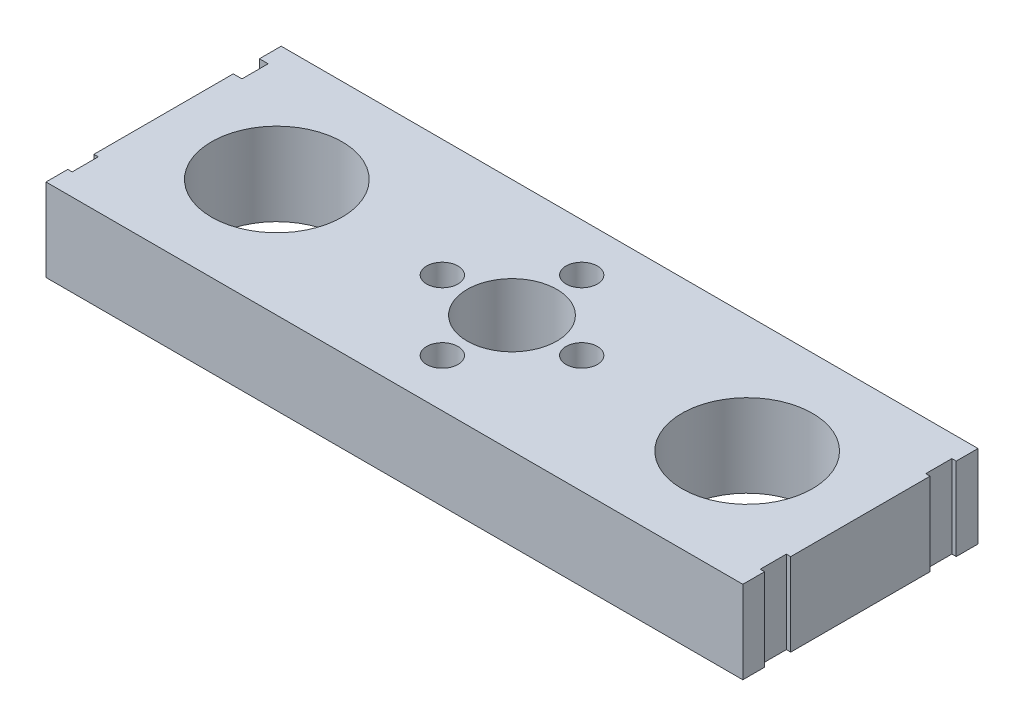
SolidWorks part; units mm, degrees
ref_plane "前视基准面" through (0, 0, 0) normal (0, 0, 1) x (1, 0, 0)
ref_plane "上视基准面" through (0, 0, 0) normal (0, 1, 0) x (1, 0, 0)
ref_plane "右视基准面" through (0, 0, 0) normal (1, 0, 0) x (0, 0, -1)
sketch "草图1" plane through (0, 0, 0) normal (0, 1, 0) x (1, 0, 0)
  line L1 (-40, 13.5) -> (40, 13.5)
  line L2 (-40, 13.5) -> (-40, -13.5)
  line L3 (-40, -13.5) -> (40, -13.5)
  line L4 (40, 13.5) -> (40, -13.5)
  line L5 (-40, 13.5) -> (40, -13.5) construction
  line L6 (-40, -13.5) -> (40, 13.5) construction
  point P0 (0, 0)
  dimension "D1" = 80
  dimension "D2" = 27
extrude "凸台-拉伸1" add sketch "草图1" along normal blind 9.5
sketch "草图2" plane through (0, 0, 0) normal (0, -1, 0) x (1, 0, 0)
  line L0 (-40, 0) -> (40, 0) construction
  line L1 (-40, -13.5) -> (-40, 13.5) construction
  line L2 (40, 13.5) -> (40, -13.5) construction
ref_plane "基准面1" through (0, 0, 0) normal (0, 0, 1) x (1, 0, 0)
sketch "草图3" plane through (0, 9.5, 0) normal (0, 1, 0) x (1, 0, 0)
  line L0 (-14.85, 0) -> (14.85, 0) construction
  line L1 (0, 13.5) -> (0, -13.5) construction
  line L2 (40, 13.5) -> (-40, 13.5) construction
  line L3 (-40, -13.5) -> (40, -13.5) construction
  circle A0 centre (-27, 0) radius 7.5
  circle A1 centre (27, 0) radius 7.5
  dimension "D1" = 15
  dimension "D2" = 54
extrude "切除-拉伸1" cut sketch "草图3" against normal through all contours A1 | A0
sketch "草图4" plane through (0, 9.5, 0) normal (0, 1, 0) x (1, 0, 0)
  line L0 (-40, 0) -> (40, 0) construction
  circle A0 centre (0, 0) radius 5.15
  dimension "D1" = 10.3
extrude "切除-拉伸2" cut sketch "草图4" against normal through all
sketch "草图5" plane through (0, 9.5, 0) normal (0, 1, 0) x (1, 0, 0)
  circle A4 centre (8, 0) radius 1.8
  circle A8 centre (-8, 0) radius 1.8
  circle A9 centre (0, 8) radius 1.8
  circle A10 centre (0, -8) radius 1.8
  dimension "D1" = 3.6
extrude "切除-拉伸3" cut sketch "草图5" against normal through all
ref_plane "基准面2" through (0, 4.5, 0) normal (0, 1, 0) x (1, 0, 0)
sketch "草图6" plane through (0, 4.5, 0) normal (0, 1, 0) x (1, 0, 0)
  line L0 (-40, 9.5) -> (40, 9.5) construction
  line L1 (-40, 13.5) -> (-40, -13.5) construction
  line L2 (40, -13.5) -> (40, 13.5) construction
  line L3 (-40, -9.5) -> (40, -9.5) construction
  line L4 (-40, -13.5) -> (40, -13.5) construction
  line L5 (40, 13.5) -> (-40, 13.5) construction
  dimension "D1" = 4
  dimension "D2" = 4
sketch "草图7" plane through (0, 9.5, 0) normal (0, 1, 0) x (1, 0, 0)
  line L0 (40, -13.5) -> (40, 13.5) construction
  line L1 (40, 11.0016) -> (39.5, 11.0016)
  line L2 (40, 11.0016) -> (40, 8.0016)
  line L3 (40, 8.0016) -> (39.5, 8.0016)
  line L4 (39.5, 11.0016) -> (39.5, 8.0016)
  line L13 (40, -7.9999) -> (39.5, -7.9999)
  line L14 (40, -7.9999) -> (40, -10.9999)
  line L15 (40, -10.9999) -> (39.5, -10.9999)
  line L16 (39.5, -7.9999) -> (39.5, -10.9999)
  line L17 (-40, 13.5) -> (-40, -13.5) construction
  line L18 (-40, 11.0016) -> (-39, 11.0016)
  line L19 (-40, 11.0016) -> (-40, 8.0016)
  line L20 (-40, 8.0016) -> (-39, 8.0016)
  line L21 (-39, 11.0016) -> (-39, 8.0016)
  line L23 (-40, -7.9999) -> (-39.5, -7.9999)
  line L24 (-40, -7.9999) -> (-40, -10.9999)
  line L25 (-40, -10.9999) -> (-39.5, -10.9999)
  line L26 (-39.5, -7.9999) -> (-39.5, -10.9999)
  dimension "D1" = 0.5
  dimension "D2" = 3
  dimension "D3" = 3
  dimension "D4" = 0.5
  dimension "D5" = 0.5
  dimension "D6" = 0.5
  dimension "D7" = 3
  dimension "D8" = 0.5
  dimension "D9" = 3
  dimension "D10" = 1
extrude "切除-拉伸4" cut sketch "草图7" against normal through all
